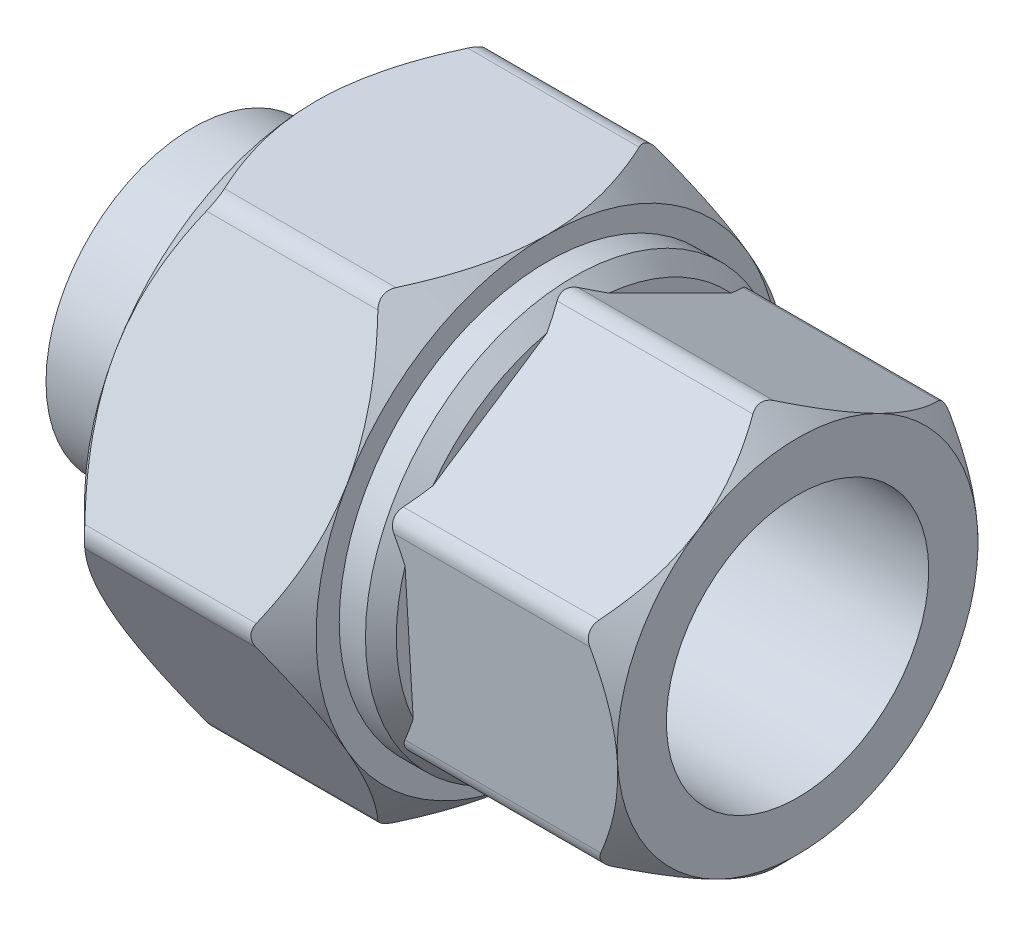
SolidWorks part; units mm, degrees
material "PE Высокой плотности"
ref_plane "Front" through (0, 0, 0) normal (0, 0, 1) x (1, 0, 0)
ref_plane "Top" through (0, 0, 0) normal (0, 1, 0) x (1, 0, 0)
ref_plane "Right" through (0, 0, 0) normal (1, 0, 0) x (0, 0, -1)
sketch "Эскиз1" plane through (0, 0, 0) normal (1, 0, 0) x (0, 0, -1)
  circle A0 centre (0, 0) radius 8
  dimension "d" = 16
extrude "Вытянуть-Тонкостенный1" add sketch "Эскиз1" along normal blind 8 thin thin type one direction wall 1.5
sketch "Эскиз2" plane through (8, 0, 0) normal (1, 0, 0) x (0, 0, -1)
  line L0 (50, 0) -> (-50, 0) construction
  line L1 (17.3205, 0) -> (8.6603, 15)
  line L2 (8.6603, 15) -> (-8.6603, 15)
  line L3 (-8.6603, 15) -> (-17.3205, 0)
  line L4 (-17.3205, 0) -> (-8.6603, -15)
  line L5 (-8.6603, -15) -> (8.6603, -15)
  line L6 (8.6603, -15) -> (17.3205, 0)
  circle A1 centre (0, 0) radius 15 construction
  dimension "D2" = 30
extrude "Бобышка-Вытянуть2" add sketch "Эскиз2" along normal blind 15
sketch "Эскиз8" plane through (8, 0, 0) normal (-1, 0, 0) x (0, 0, 1)
  circle A0 centre (0, 0) radius 15 construction
  circle A1 centre (0, 0) radius 15
extrude "Вырез-Вытянуть4" cut sketch "Эскиз8" against normal blind 10 draft 45 flip side to cut
sketch "Эскиз9" plane through (23, 0, 0) normal (1, 0, 0) x (0, 0, -1)
  circle A0 centre (0, 0) radius 15 construction
  circle A1 centre (0, 0) radius 15
extrude "Вырез-Вытянуть5" cut sketch "Эскиз9" against normal blind 10 draft 45 flip side to cut
sketch "Эскиз10" plane through (23, 0, 0) normal (1, 0, 0) x (0, 0, -1)
  circle A0 centre (0, 0) radius 13.5
  dimension "R1" = 27
extrude "Бобышка-Вытянуть3" add sketch "Эскиз10" along normal blind 2.7
sketch "Эскиз11" plane through (25.7, 0, 0) normal (1, 0, 0) x (0, 0, -1)
  line L1 (0.8039, -13.476) -> (12.0725, -6.0418)
  line L2 (12.0725, -6.0418) -> (11.2687, 7.4342)
  line L3 (11.2687, 7.4342) -> (-0.8039, 13.476)
  line L4 (-0.8039, 13.476) -> (-12.0725, 6.0418)
  line L5 (-12.0725, 6.0418) -> (-11.2687, -7.4342)
  line L6 (-11.2687, -7.4342) -> (0.8039, -13.476)
  circle A0 centre (0, 0) radius 11.6913 construction
  circle A1 centre (0, 0) radius 13.5 construction
  circle A2 centre (0, 0) radius 13.5 construction
extrude "Бобышка-Вытянуть4" add sketch "Эскиз11" along normal blind 13.5
sketch "Эскиз12" plane through (39.2, 0, 0) normal (1, 0, 0) x (0, 0, -1)
  circle A0 centre (0, 0) radius 11.6913 construction
  circle A1 centre (0, 0) radius 11.6913
extrude "Вырез-Вытянуть6" cut sketch "Эскиз12" against normal blind 13.5 draft 45 flip side to cut
fillet "Скругление1" radius 1.35 12 edges at (15.5, 15, -8.6603) (15.5, 0, -17.3205) (15.5, -15, -8.6603) (15.5, -15, 8.6603) (15.5, 15, 8.6603) (15.5, 0, 17.3205) (31.5457, -13.476, -0.8039) (31.5457, -7.4342, 11.2687) (31.5457, 6.0418, 12.0725) (31.5457, -6.0418, -12.0725) (31.5457, 7.4342, -11.2687) (31.5457, 13.476, 0.8039)
chamfer "Фаска1" distance 1 angle 45 6 edges at (25.7, 12.0725, -6.0418) (25.7, 11.2687, 7.4342) (25.7, -0.8039, 13.476) (25.7, -12.0725, 6.0418) (25.7, -11.2687, -7.4342) (25.7, 0.8039, -13.476)
sketch "Эскиз13" plane through (39.2, 0, 0) normal (1, 0, 0) x (0, 0, -1)
  circle A0 centre (0, 0) radius 8.5
  dimension "R" = 17
extrude "Вырез-Вытянуть7" cut sketch "Эскиз13" against normal blind 15
sketch3d "Трехмерный эскиз1"
  line L0 (0, 0, 0) -> (39.2, 0, 0) construction
other "Точка соединения1" parameters "Диаметр"=16, "StubLength"=0
ref_axis "Ось1" through (-10, 0, 0) along (1, 0, 0)
